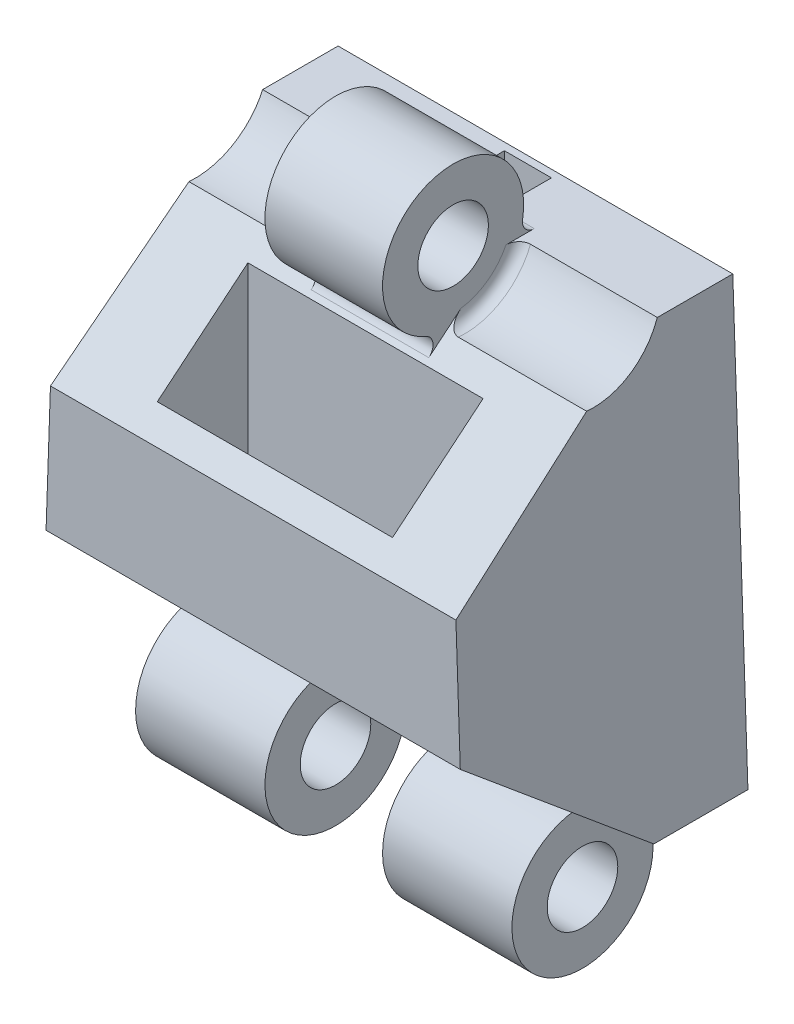
SolidWorks part; units mm, degrees
ref_plane "Front Plane" through (0, 0, 0) normal (0, 0, 1) x (1, 0, 0)
ref_plane "Top Plane" through (0, 0, 0) normal (0, 1, 0) x (1, 0, 0)
ref_plane "Right Plane" through (0, 0, 0) normal (1, 0, 0) x (0, 0, -1)
sketch "Sketch1" plane through (0, 0, 0) normal (0, 0, 1) x (1, 0, 0)
  line L0 (-8, -14.5) -> (-6.9661, 15.4822)
  line L3 (-8, -14.5) -> (10.0677, -14.5)
  line L5 (10.0677, -14.5) -> (9.0339, 15.4822)
  line L6 (-6.9661, 15.4822) -> (9.0339, 15.4822)
  point P0 (0, 0)
extrude "Boss-Extrude2" add sketch "Sketch1" along normal blind 12
sketch "Sketch15" plane through (0, 0, 0) normal (0, 0, -1) x (-1, 0, 0)
  line L0 (6.9661, 15.4822) -> (-9.0339, 15.4822)
  line L1 (-1.0339, 15.4822) -> (-1.0339, 5.488)
ref_plane "Plane1" through (1.0339, 0, 0) normal (1, 0, 0) x (0, 0, -1)
sketch "Sketch16" plane through (1.0339, 0, 0) normal (1, 0, 0) x (0, 0, -1)
  line L0 (0, 15.4822) -> (-4, 15.4822)
  line L6 (-12, 15.4822) -> (0, 15.4822) construction
  line L7 (-4, 15.4822) -> (-12, 8.8525)
  line L8 (-12, -14.5) -> (-12, 15.4822) construction
  line L9 (-12, 8.8525) -> (-12, 15.4822)
  line L10 (-12, 15.4822) -> (-4, 15.4822)
extrude "Cut-Extrude2" cut sketch "Sketch16" against normal through all both and the other way through all contours L10 L9 L7 region at (1.0339, 13.2723, 9.3333)
sketch "Sketch17" plane through (1.0339, 0, 0) normal (1, 0, 0) x (0, 0, -1)
  line L0 (-12, 8.8525) -> (-12, 18.723)
  line L1 (0, 15.4822) -> (-12, 15.4822)
  line L2 (-6, 15.4822) -> (-6, 16.5822)
  circle A0 centre (-6, 16.5822) radius 1.5
  circle A1 centre (-6, 16.5822) radius 3
extrude "Boss-Extrude3" add sketch "Sketch17" along normal mid plane 5 contours L1 A1 A0 | L1 A1 A0 region at (1.0339, 14.6478, 6) region at (1.0339, 15.5549, 4.0946)
sketch "Sketch18" plane through (1.0339, 0, 0) normal (1, 0, 0) x (0, 0, -1)
  line L0 (0, -14.5) -> (-4, -14.5)
  line L1 (-12, -14.5) -> (0, -14.5) construction
  line L2 (-4, -14.5) -> (-12, -7.8704)
  line L3 (-12, -14.5) -> (-12, 8.8525) construction
  line L4 (-12, -7.8704) -> (-12, -14.5)
  line L5 (-12, -14.5) -> (-4, -14.5)
extrude "Cut-Extrude3" cut sketch "Sketch18" against normal through all both and the other way through all contours L4 L5 L2 region at (1.0339, -12.2901, 9.3333)
sketch "Sketch19" plane through (1.0339, 0, 0) normal (1, 0, 0) x (0, 0, -1)
  line L0 (-12, -7.8704) -> (-12, -19.6668)
  line L1 (0, -14.5) -> (-3.2089, -14.5)
  line L3 (-8.7911, -14.5) -> (-12, -14.5)
  circle A0 centre (-6, -15.6) radius 1.5
  circle A1 centre (-6, -15.6) radius 3
extrude "Boss-Extrude4" add sketch "Sketch19" along normal mid plane 16 contours A1 A0 region at (1.0339, -18.4639, 6.544)
extrude "Cut-Extrude4" cut sketch "Sketch19<3>" against normal mid plane 5 contours A1
sketch "Sketch19<3>" plane through (1.0339, 0, 0) normal (1, 0, 0) x (0, 0, -1) same geometry as "Sketch19"
sketch "Sketch20" plane through (3.5339, 0, 0) normal (1, 0, 0) x (0, 0, -1)
  circle A0 centre (-6, 16.5822) radius 3
extrude "Cut-Extrude5" cut sketch "Sketch20" along normal blind 10
sketch "Sketch21" plane through (-1.4661, 0, 0) normal (-1, 0, 0) x (0, 0, 1)
  circle A0 centre (6, 16.5822) radius 3
extrude "Cut-Extrude6" cut sketch "Sketch21" along normal blind 10
fillet "Fillet6" radius 0.5 1 edges at (1.0339, 13.595, 6.2772)
fillet "Fillet7" radius 0.5 1 edges at (1.0339, 15.4822, 3.2089)
fillet "Fillet8" radius 0.5 2 edges at (3.5339, 14.0268, 4.4283) (-1.4661, 14.0268, 4.4283)
sketch "Sketch23" plane through (1.0339, 0, 0) normal (1, 0, 0) x (0, 0, -1)
  line L0 (0, 4.1674) -> (0, 23.256)
  line L2 (0, 23.256) -> (-12, 23.256)
  line L3 (-12, -2.4623) -> (-4, 4.1674)
  line L5 (-12, -7.8704) -> (-12, 8.8525) construction
  line L6 (-4, 4.1674) -> (0, 4.1674)
  line L7 (0, -14.5) -> (0, 15.4822) construction
  line L8 (-12, 23.256) -> (-12, -2.4623)
extrude "Cut-Extrude8" cut sketch "Sketch23" against normal through all both and the other way through all
sketch "Sketch26" plane through (1.0339, 0, 0) normal (1, 0, 0) x (0, 0, -1)
  line L0 (-6, 4.1674) -> (-6, 5.2674)
  line L1 (-4, 4.1674) -> (-6, 4.1674)
  line L2 (-6, 4.1674) -> (-6, 5.2674)
  circle A0 centre (-6, 5.2674) radius 1.5
  circle A1 centre (-6, 5.2674) radius 3
extrude "Cut-Extrude9" cut sketch "Sketch26" against normal through all both and the other way through all contours A1 A0 region at (1.0339, 5.2674, 8.9151)
sketch "Sketch27" plane through (1.0339, 0, 0) normal (1, 0, 0) x (0, 0, -1)
  circle A0 centre (-6, 5.2674) radius 1.5
  circle A1 centre (-6, 5.2674) radius 3
extrude "Boss-Extrude6" add sketch "Sketch27" along normal mid plane 5
fillet "Fillet9" radius 0.5 2 edges at (1.0339, 4.1674, 3.2089) (1.0339, 2.2802, 6.2772)
fillet "Fillet10" radius 0.5 2 edges at (-1.4661, 2.712, 4.4283) (3.5339, 2.712, 4.4283)
sketch "Sketch28" plane through (0, 4.4359, 3.676) normal (0, 0.77, 0.6381) x (1, 0, 0)
  line L0 (1.0339, -10.8108) -> (1.0339, -9.6108)
  line L1 (9.6526, -10.8108) -> (-7.5849, -10.8108) construction
  line L2 (1.0339, -9.6108) -> (6.0339, -9.6108)
  line L3 (6.0339, -9.6108) -> (6.0339, -4.6108)
  line L4 (6.0339, -4.6108) -> (-3.9661, -4.6108)
  line L5 (-3.9661, -4.6108) -> (-3.9661, -9.6108)
  line L6 (-3.9661, -9.6108) -> (1.0339, -9.6108)
ref_plane "Plane2" through (0, -5, 0) normal (0, 1, 0) x (1, 0, 0)
sketch "Sketch29" plane through (0, -5, 0) normal (0, 1, 0) x (1, 0, 0)
  line L0 (-3.9661, -7.2262) -> (-3.9661, -11.076)
  line L1 (-3.9661, -11.076) -> (6.0339, -11.076)
  line L2 (6.0339, -11.076) -> (6.0339, -7.2262)
  line L3 (6.0339, -7.2262) -> (-3.9661, -7.2262)
extrude "Cut-Extrude10" cut sketch "Sketch29" against normal up to surface and the other way up to surface up to face at (1.0339, -12.4192, 6.5109) other way up to face at (1.0451, 1.2769, 7.4879)
sketch "Sketch30" plane through (1.0339, 0, 0) normal (1, 0, 0) x (0, 0, -1)
  line L0 (0, 4.1674) -> (-2.32, 4.1674)
  line L1 (0, 4.1674) -> (-3.2089, 4.1674) construction
  line L2 (-2.32, 4.1674) -> (-2.32, -17.5788)
  line L3 (-2.32, -17.5788) -> (-0.32, -17.5788)
  line L4 (-0.32, -17.5788) -> (-0.32, 6.5359)
extrude "Cut-Extrude11" cut sketch "Sketch30" against normal mid plane 2 contours L3 L4 L0 L2 region at (1.0339, -6.7057, 1.32)
